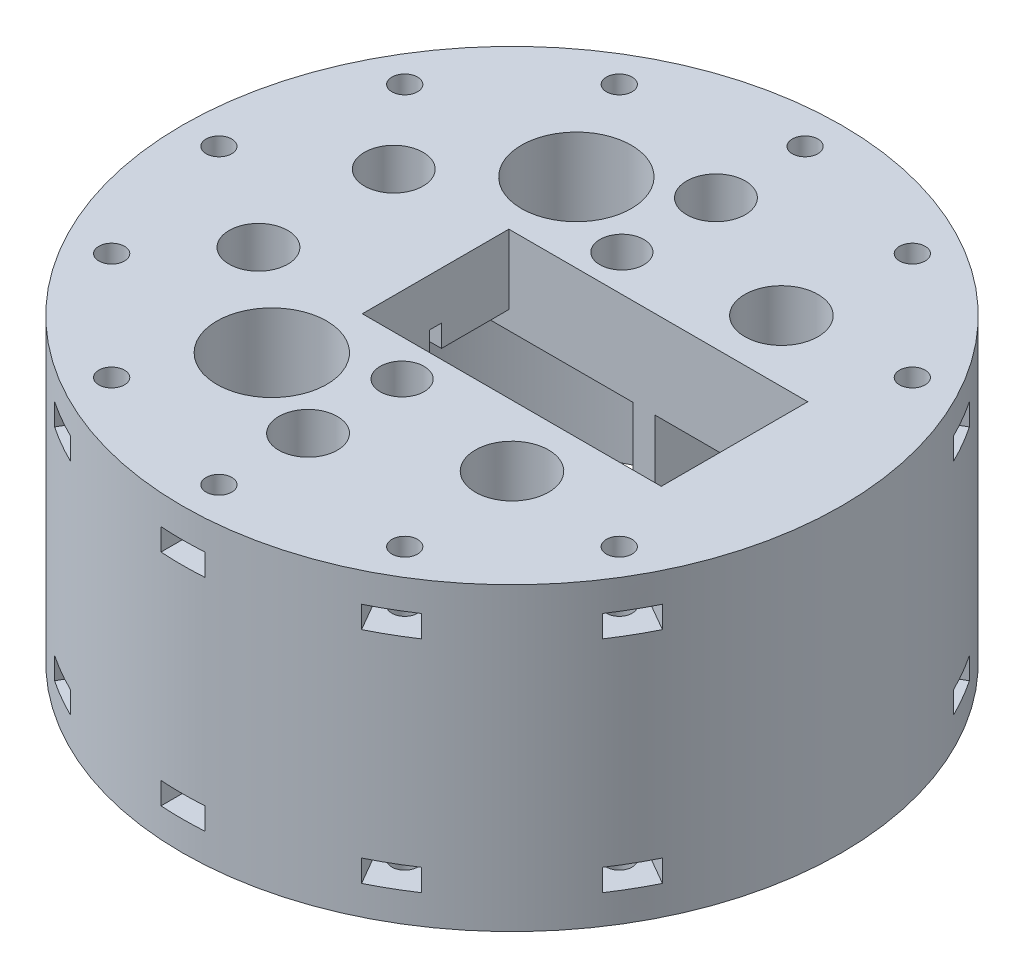
SolidWorks part; units mm, degrees
ref_plane "Front Plane" through (0, 0, 0) normal (0, 0, 1) x (1, 0, 0)
ref_plane "Top Plane" through (0, 0, 0) normal (0, 1, 0) x (1, 0, 0)
ref_plane "Right Plane" through (0, 0, 0) normal (1, 0, 0) x (0, 0, -1)
sketch "Sketch1" plane through (0, 0, 0) normal (0, 1, 0) x (1, 0, 0)
  line L0 (-43.0464, 0) -> (41.9462, 0) construction
  line L1 (0, 43.1152) -> (0, -41.8775) construction
  circle A1 centre (0, 0) radius 45
  dimension "D2" = 90
extrude "Boss-Extrude1" add sketch "Sketch1" along normal blind 41
sketch "Sketch2" plane through (0, 0, 0) normal (0, -1, 0) x (1, 0, 0)
  circle A0 centre (0, 0) radius 35
  dimension "D1" = 70
extrude "Cut-Extrude1" cut sketch "Sketch2" against normal blind 29
sketch "Sketch3" plane through (0, 29, 0) normal (0, -1, 0) x (1, 0, 0)
  line L0 (35, 0) -> (-35, 0) construction
  line L1 (0, -35) -> (0, 35) construction
  line L3 (37.5324, -10) -> (-17.4676, -10)
  line L4 (37.5324, -10) -> (37.5324, 10)
  line L5 (37.5324, 10) -> (-17.4676, 10)
  line L6 (-17.4676, -10) -> (-17.4676, 10)
  circle A0 centre (0, 0) radius 35 construction
  circle A1 centre (0, 0) radius 35 construction
  dimension "D1" = 20
  dimension "D2" = 55
  dimension "D3" = 10
  dimension "D4" = 37.5324
extrude "Cut-Extrude2" cut sketch "Sketch3" against normal blind 2.5 and the other way up to next
sketch "Sketch4" plane through (0, 31.5, 0) normal (0, -1, 0) x (1, 0, 0)
  line L0 (37.5324, 0) -> (-17.4676, 0) construction
  line L1 (37.5324, 10) -> (37.5324, -10) construction
  line L2 (-17.4676, 10) -> (-17.4676, -10) construction
  line L3 (0, -10) -> (0, 10) construction
  line L4 (-17.4676, -10) -> (33.541, -10) construction
  line L5 (33.541, 10) -> (-17.4676, 10) construction
  line L7 (30.3722, -10) -> (-10.4278, -10)
  line L8 (30.3722, -10) -> (30.3722, 10)
  line L9 (30.3722, 10) -> (-10.4278, 10)
  line L10 (-10.4278, -10) -> (-10.4278, 10)
  dimension "D1" = 20
  dimension "D2" = 40.8
  dimension "D3" = 30.3722
  dimension "D4" = 10
extrude "Cut-Extrude3" cut sketch "Sketch4" against normal blind 12.5
sketch "Sketch8" plane through (0, 29, 0) normal (0, -1, 0) x (1, 0, 0)
  line L0 (-17.4676, 0) -> (-35, 0) construction
  line L1 (-17.4676, 10) -> (-17.4676, -10) construction
  line L2 (8.0367, 10) -> (8.0367, 34.0648) construction
  line L3 (33.541, 10) -> (-17.4676, 10) construction
  line L4 (8.0367, -10) -> (8.0367, -29.3194) construction
  line L5 (-17.4676, -10) -> (33.541, -10) construction
  line L6 (6.5367, 10) -> (6.5367, 34.3842)
  line L7 (9.5367, 10) -> (9.5367, 33.6757)
  line L8 (9.5367, 10) -> (6.5367, 10)
  line L9 (9.5367, -10) -> (6.5367, -10)
  line L10 (6.5367, -10) -> (6.5367, -34.3842)
  line L11 (9.5367, -10) -> (9.5367, -33.6757)
  line L12 (-17.4676, 1.5) -> (-34.9678, 1.5)
  line L13 (-17.4676, -1.5) -> (-34.9678, -1.5)
  line L14 (-17.4676, 1.5) -> (-17.4676, -1.5)
  arc A0 (33.541, 10) -> (33.541, -10) centre (0, 0) ccw construction
  arc A1 (9.5367, 33.6757) -> (6.5367, 34.3842) centre (7.9531, 33.6757) ccw
  arc A2 (9.5367, -33.6757) -> (6.5367, -34.3842) centre (7.9531, -33.6757) cw
  arc A3 (-34.9678, 1.5) -> (-34.9678, -1.5) centre (-34.9678, 0) ccw
  dimension "D3" = 1.5
  dimension "D1" = 1.5
  dimension "D2" = 1.5
  dimension "D4" = 1.5
extrude "Boss-Extrude2" add sketch "Sketch8" along normal through all
sketch "Sketch13" plane through (0, 29, 0) normal (0, -1, 0) x (1, 0, 0)
  line L0 (0, 0) -> (0, 35) construction
  line L1 (0, 0) -> (-17.5, 30.3109) construction
  line L2 (0, 0) -> (-41.2446, 0) construction
  line L3 (-32.8892, 11.9707) -> (0, 0) construction
  line L5 (0, 0) -> (24.7487, 24.7487) construction
  arc A0 (6.5367, 34.3842) -> (-34.9678, 1.5) centre (0, 0) ccw construction
  circle A1 centre (-12, 20.7846) radius 7.5
  circle A2 centre (-25.3717, 9.2345) radius 4
  arc A3 (33.541, 10) -> (9.5367, 33.6757) centre (0, 0) ccw construction
  circle A4 centre (18.3848, 18.3848) radius 5
  circle A5 centre (18.3848, -18.3848) radius 5
  circle A6 centre (-12, -20.7846) radius 7.5
  circle A7 centre (-25.3717, -9.2345) radius 4
  circle A8 centre (0, -15) radius 3
  circle A9 centre (0, -27.8351) radius 4
  circle A10 centre (0, 27.8351) radius 4
  circle A11 centre (0, 15) radius 3
  dimension "D3" = 15
  dimension "D6" = 8
  dimension "D8" = 10
  dimension "D10" = 8
  dimension "D11" = 6
  dimension "D1" = 30
  dimension "D2" = 20
  dimension "D4" = 27
  dimension "D5" = 24
  dimension "D7" = 45
  dimension "D9" = 26
  dimension "D12" = 15
extrude "Cut-Extrude7" cut sketch "Sketch13" against normal through all
sketch "Sketch15" plane through (0, 0, -1.5) normal (0, 0, -1) x (-1, 0, 0)
  line L0 (34.9678, 0) -> (17.4676, 29)
  line L1 (17.4676, 29) -> (17.4676, 0)
  line L3 (17.4676, 0) -> (34.9678, 0)
extrude "Cut-Extrude8" cut sketch "Sketch15" against normal blind 3
sketch "Sketch16" plane through (0, 31.5, 0) normal (0, -1, 0) x (1, 0, 0)
  line L0 (-17.4676, 0) -> (37.5324, 0) construction
  line L1 (-17.4676, 10) -> (-17.4676, -10) construction
  line L2 (37.5324, -10) -> (37.5324, 10) construction
  line L3 (30.3722, -0.8) -> (37.5324, -0.8)
  line L4 (-10.4278, -0.8) -> (-17.4676, -0.8)
  line L5 (-10.4278, 10) -> (-10.4278, -10) construction
  line L6 (-10.4278, 0.8) -> (-17.4676, 0.8)
  line L7 (-17.4676, 0.8) -> (-17.4676, -0.8)
  line L8 (-10.4278, 0.8) -> (-10.4278, -0.8)
  line L9 (30.3722, -10) -> (30.3722, 10) construction
  line L10 (30.3722, 0.8) -> (37.5324, 0.8)
  line L11 (37.5324, 0.8) -> (37.5324, -0.8)
  line L12 (30.3722, 0.8) -> (30.3722, -0.8)
  dimension "D1" = 0.8
extrude "Cut-Extrude10" cut sketch "Sketch16" against normal blind 3
sketch "Sketch27" plane through (0, 0, 0) normal (0, -1, 0) x (1, 0, 0)
  line L0 (0, 0) -> (0, -53.17) construction
  line L1 (0, 0) -> (47.7582, -27.5732) construction
  line L3 (31.641, -18.2679) -> (31.641, -21.7321) construction
  line L4 (31.641, -21.7321) -> (34.641, -23.4641) construction
  line L5 (34.641, -23.4641) -> (37.641, -21.7321) construction
  line L6 (37.641, -21.7321) -> (37.641, -18.2679) construction
  line L7 (37.641, -18.2679) -> (34.641, -16.5359) construction
  line L8 (34.641, -16.5359) -> (31.641, -18.2679) construction
  circle A0 centre (0, 0) radius 40 construction
  circle A1 centre (34.641, -20) radius 1.75
  circle A2 centre (0, 0) radius 35 construction
  circle A3 centre (34.641, -20) radius 3 construction
  circle A4 centre (20, -34.641) radius 1.75
  circle A5 centre (0, -40) radius 1.75
  circle A6 centre (-20, -34.641) radius 1.75
  circle A7 centre (-34.641, -20) radius 1.75
  circle A8 centre (-40, 0) radius 1.75
  circle A9 centre (-34.641, 20) radius 1.75
  circle A10 centre (-20, 34.641) radius 1.75
  circle A11 centre (0, 40) radius 1.75
  circle A12 centre (20, 34.641) radius 1.75
  circle A13 centre (34.641, 20) radius 1.75
  circle A15 centre (40, 0) radius 1.75 [skipped]
  point P28 (0, 0)
  point P41 (0, 0)
  dimension "D1" = 80
  dimension "D3" = 3.5
  dimension "D4" = 70
  dimension "D5" = 6
  dimension "D6" = 12
  dimension "D2" = 60
extrude "Cut-Extrude15" cut sketch "Sketch27" against normal through all
ref_plane "Plane1" through (0, 37, 0) normal (0, 1, 0) x (1, 0, 0)
sketch "Sketch28" plane through (0, 37, 0) normal (0, 1, 0) x (1, 0, 0)
  line L0 (0, 0) -> (-54.493, 0) construction
  line L1 (-31.641, 18.2679) -> (-31.641, 21.7321)
  line L2 (-36.5359, 0) -> (-38.2679, 3)
  line L3 (-38.2679, 3) -> (-44.8999, 3)
  line L4 (-31.641, 21.7321) -> (-37.3844, 25.048)
  line L5 (-40.3844, 19.8519) -> (-34.641, 16.5359)
  line L6 (-44.8999, -3) -> (-38.2679, -3)
  line L7 (-38.2679, -3) -> (-36.5359, 0)
  line L8 (-43.4641, 0) -> (-42.5981, -1.5) [skipped]
  line L9 (-41.7321, 3) -> (-42.5981, 1.5) [skipped]
  line L10 (-34.641, 16.5359) -> (-31.641, 18.2679)
  line L11 (-18.2679, 31.641) -> (-16.5359, 34.641)
  line L12 (-16.5359, 34.641) -> (-19.8519, 40.3844)
  line L13 (-25.048, 37.3844) -> (-21.7321, 31.641)
  line L14 (-21.7321, 31.641) -> (-18.2679, 31.641)
  line L15 (0, 36.5359) -> (3, 38.2679)
  line L16 (3, 38.2679) -> (3, 44.8999)
  line L17 (-3, 44.8999) -> (-3, 38.2679)
  line L18 (-3, 38.2679) -> (0, 36.5359)
  line L19 (18.2679, 31.641) -> (21.7321, 31.641)
  line L20 (21.7321, 31.641) -> (25.048, 37.3844)
  line L21 (19.8519, 40.3844) -> (16.5359, 34.641)
  line L22 (16.5359, 34.641) -> (18.2679, 31.641)
  line L23 (31.641, 18.2679) -> (34.641, 16.5359)
  line L24 (34.641, 16.5359) -> (40.3844, 19.8519)
  line L25 (37.3844, 25.048) -> (31.641, 21.7321)
  line L26 (31.641, 21.7321) -> (31.641, 18.2679)
  line L31 (31.641, -18.2679) -> (31.641, -21.7321)
  line L32 (31.641, -21.7321) -> (37.3844, -25.048)
  line L33 (40.3844, -19.8519) -> (34.641, -16.5359)
  line L34 (34.641, -16.5359) -> (31.641, -18.2679)
  line L35 (18.2679, -31.641) -> (16.5359, -34.641)
  line L36 (16.5359, -34.641) -> (19.8519, -40.3844)
  line L37 (25.048, -37.3844) -> (21.7321, -31.641)
  line L38 (21.7321, -31.641) -> (18.2679, -31.641)
  line L39 (0, -36.5359) -> (-3, -38.2679)
  line L40 (-3, -38.2679) -> (-3, -44.8999)
  line L41 (3, -44.8999) -> (3, -38.2679)
  line L42 (3, -38.2679) -> (0, -36.5359)
  line L43 (-18.2679, -31.641) -> (-21.7321, -31.641)
  line L44 (-21.7321, -31.641) -> (-25.048, -37.3844)
  line L45 (-19.8519, -40.3844) -> (-16.5359, -34.641)
  line L46 (-16.5359, -34.641) -> (-18.2679, -31.641)
  line L47 (-31.641, -18.2679) -> (-34.641, -16.5359)
  line L48 (-34.641, -16.5359) -> (-40.3844, -19.8519)
  line L49 (-37.3844, -25.048) -> (-31.641, -21.7321)
  line L50 (-31.641, -21.7321) -> (-31.641, -18.2679)
  line L51 (36.5359, 0) -> (38.2679, -3) [skipped]
  line L52 (38.2679, -3) -> (44.8999, -3) [skipped]
  line L53 (44.8999, 3) -> (38.2679, 3) [skipped]
  line L54 (38.2679, 3) -> (36.5359, 0) [skipped]
  arc A0 (-44.8999, 3) -> (-44.8999, -3) centre (0, 0) ccw
  circle A1 centre (-40, 0) radius 3 construction
  arc A2 (-37.3844, 25.048) -> (-40.3844, 19.8519) centre (0, 0) ccw
  circle A3 centre (-34.641, 20) radius 3 construction
  arc A4 (-19.8519, 40.3844) -> (-25.048, 37.3844) centre (0, 0) ccw
  circle A5 centre (-20, 34.641) radius 3 construction
  arc A6 (3, 44.8999) -> (-3, 44.8999) centre (0, 0) ccw
  circle A7 centre (0, 40) radius 3 construction
  arc A8 (25.048, 37.3844) -> (19.8519, 40.3844) centre (0, 0) ccw
  circle A9 centre (20, 34.641) radius 3 construction
  arc A10 (40.3844, 19.8519) -> (37.3844, 25.048) centre (0, 0) ccw
  circle A11 centre (34.641, 20) radius 3 construction
  arc A14 (37.3844, -25.048) -> (40.3844, -19.8519) centre (0, 0) ccw
  circle A15 centre (34.641, -20) radius 3 construction
  arc A16 (19.8519, -40.3844) -> (25.048, -37.3844) centre (0, 0) ccw
  circle A17 centre (20, -34.641) radius 3 construction
  arc A18 (-3, -44.8999) -> (3, -44.8999) centre (0, 0) ccw
  circle A19 centre (0, -40) radius 3 construction
  arc A20 (-25.048, -37.3844) -> (-19.8519, -40.3844) centre (0, 0) ccw
  circle A21 centre (-20, -34.641) radius 3 construction
  arc A22 (-40.3844, -19.8519) -> (-37.3844, -25.048) centre (0, 0) ccw
  circle A23 centre (-34.641, -20) radius 3 construction
  arc A24 (44.8999, -3) -> (44.8999, 3) centre (0, 0) ccw [skipped]
  circle A25 centre (40, 0) radius 3 construction
  point P94 (0, 0)
  dimension "D1" = 90
  dimension "D2" = 6
  dimension "D3" = 12
extrude "Cut-Extrude17" cut sketch "Sketch28" against normal blind 3
ref_plane "Plane2" through (0, 4, 0) normal (0, -1, 0) x (-1, 0, 0)
sketch "Sketch30" plane through (0, 4, 0) normal (0, -1, 0) x (-1, 0, 0)
  line L0 (0, 0) -> (56.1913, 0) construction
  line L1 (31.641, -18.2679) -> (31.641, -21.7321)
  line L2 (36.5359, 0) -> (38.2679, -3)
  line L3 (38.2679, -3) -> (44.8999, -3)
  line L4 (31.641, -21.7321) -> (37.3844, -25.048)
  line L5 (40.3844, -19.8519) -> (34.641, -16.5359)
  line L6 (44.8999, 3) -> (38.2679, 3)
  line L7 (38.2679, 3) -> (36.5359, 0)
  line L8 (43.4641, 0) -> (42.5981, 1.5) [skipped]
  line L9 (41.7321, -3) -> (42.5981, -1.5) [skipped]
  line L10 (34.641, -16.5359) -> (31.641, -18.2679)
  line L11 (18.2679, -31.641) -> (16.5359, -34.641)
  line L12 (16.5359, -34.641) -> (19.8519, -40.3844)
  line L13 (25.048, -37.3844) -> (21.7321, -31.641)
  line L14 (21.7321, -31.641) -> (18.2679, -31.641)
  line L15 (0, -36.5359) -> (-3, -38.2679)
  line L16 (-3, -38.2679) -> (-3, -44.8999)
  line L17 (3, -44.8999) -> (3, -38.2679)
  line L18 (3, -38.2679) -> (0, -36.5359)
  line L19 (-18.2679, -31.641) -> (-21.7321, -31.641)
  line L20 (-21.7321, -31.641) -> (-25.048, -37.3844)
  line L21 (-19.8519, -40.3844) -> (-16.5359, -34.641)
  line L22 (-16.5359, -34.641) -> (-18.2679, -31.641)
  line L23 (-31.641, -18.2679) -> (-34.641, -16.5359)
  line L24 (-34.641, -16.5359) -> (-40.3844, -19.8519)
  line L25 (-37.3844, -25.048) -> (-31.641, -21.7321)
  line L26 (-31.641, -21.7321) -> (-31.641, -18.2679)
  line L31 (-31.641, 18.2679) -> (-31.641, 21.7321)
  line L32 (-31.641, 21.7321) -> (-37.3844, 25.048)
  line L33 (-40.3844, 19.8519) -> (-34.641, 16.5359)
  line L34 (-34.641, 16.5359) -> (-31.641, 18.2679)
  line L35 (-18.2679, 31.641) -> (-16.5359, 34.641)
  line L36 (-16.5359, 34.641) -> (-19.8519, 40.3844)
  line L37 (-25.048, 37.3844) -> (-21.7321, 31.641)
  line L38 (-21.7321, 31.641) -> (-18.2679, 31.641)
  line L39 (0, 36.5359) -> (3, 38.2679)
  line L40 (3, 38.2679) -> (3, 44.8999)
  line L41 (-3, 44.8999) -> (-3, 38.2679)
  line L42 (-3, 38.2679) -> (0, 36.5359)
  line L43 (18.2679, 31.641) -> (21.7321, 31.641)
  line L44 (21.7321, 31.641) -> (25.048, 37.3844)
  line L45 (19.8519, 40.3844) -> (16.5359, 34.641)
  line L46 (16.5359, 34.641) -> (18.2679, 31.641)
  line L47 (31.641, 18.2679) -> (34.641, 16.5359)
  line L48 (34.641, 16.5359) -> (40.3844, 19.8519)
  line L49 (37.3844, 25.048) -> (31.641, 21.7321)
  line L50 (31.641, 21.7321) -> (31.641, 18.2679)
  line L51 (-36.5359, 0) -> (-38.2679, 3) [skipped]
  line L52 (-38.2679, 3) -> (-44.8999, 3) [skipped]
  line L53 (-44.8999, -3) -> (-38.2679, -3) [skipped]
  line L54 (-38.2679, -3) -> (-36.5359, 0) [skipped]
  arc A0 (44.8999, -3) -> (44.8999, 3) centre (0, 0) ccw
  circle A1 centre (40, 0) radius 3 construction
  arc A2 (37.3844, -25.048) -> (40.3844, -19.8519) centre (0, 0) ccw
  circle A3 centre (34.641, -20) radius 3 construction
  arc A4 (19.8519, -40.3844) -> (25.048, -37.3844) centre (0, 0) ccw
  circle A5 centre (20, -34.641) radius 3 construction
  arc A6 (-3, -44.8999) -> (3, -44.8999) centre (0, 0) ccw
  circle A7 centre (0, -40) radius 3 construction
  arc A8 (-25.048, -37.3844) -> (-19.8519, -40.3844) centre (0, 0) ccw
  circle A9 centre (-20, -34.641) radius 3 construction
  arc A10 (-40.3844, -19.8519) -> (-37.3844, -25.048) centre (0, 0) ccw
  circle A11 centre (-34.641, -20) radius 3 construction
  arc A14 (-37.3844, 25.048) -> (-40.3844, 19.8519) centre (0, 0) ccw
  circle A15 centre (-34.641, 20) radius 3 construction
  arc A16 (-19.8519, 40.3844) -> (-25.048, 37.3844) centre (0, 0) ccw
  circle A17 centre (-20, 34.641) radius 3 construction
  arc A18 (3, 44.8999) -> (-3, 44.8999) centre (0, 0) ccw
  circle A19 centre (0, 40) radius 3 construction
  arc A20 (25.048, 37.3844) -> (19.8519, 40.3844) centre (0, 0) ccw
  circle A21 centre (20, 34.641) radius 3 construction
  arc A22 (40.3844, 19.8519) -> (37.3844, 25.048) centre (0, 0) ccw
  circle A23 centre (34.641, 20) radius 3 construction
  arc A24 (-44.8999, 3) -> (-44.8999, -3) centre (0, 0) ccw [skipped]
  circle A25 centre (-40, 0) radius 3 construction
  point P94 (0, 0)
  dimension "D1" = 90
  dimension "D2" = 6
  dimension "D3" = 12
extrude "Cut-Extrude19" cut sketch "Sketch30" against normal blind 3
